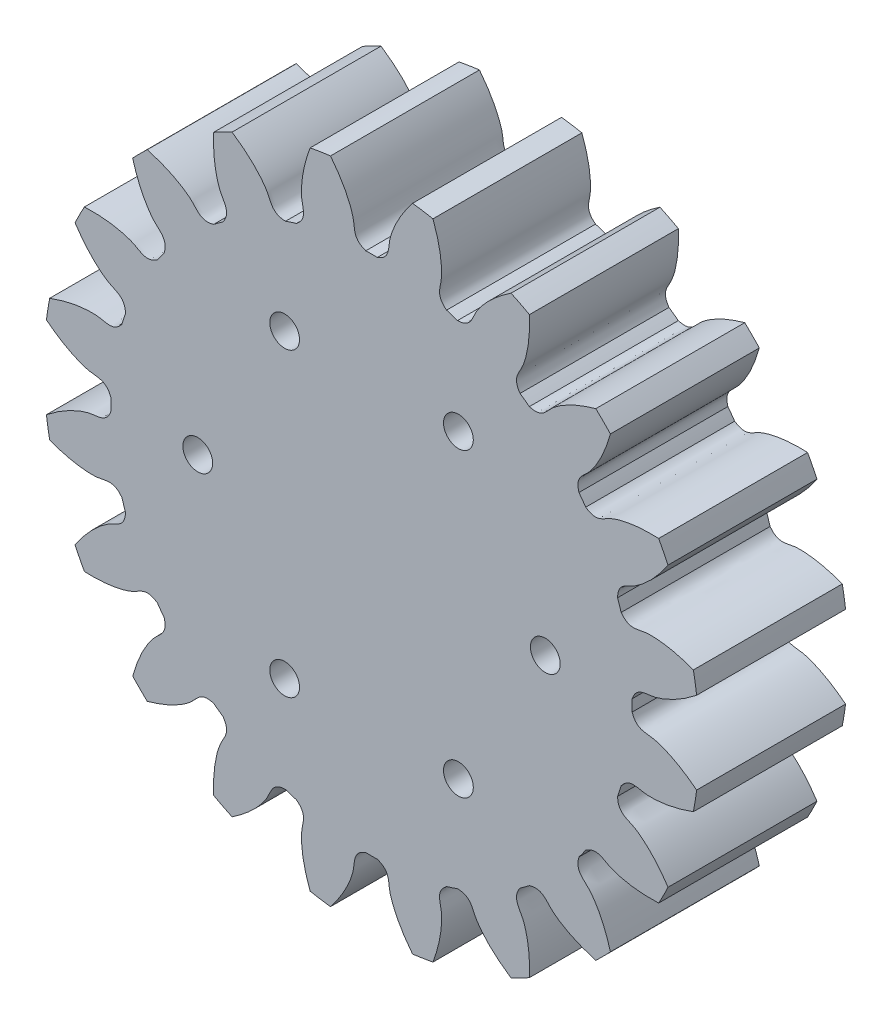
SolidWorks part; units mm, degrees
ref_plane "前视基准面" through (0, 0, 0) normal (0, 0, 1) x (1, 0, 0)
ref_plane "上视基准面" through (0, 0, 0) normal (0, 1, 0) x (1, 0, 0)
ref_plane "右视基准面" through (0, 0, 0) normal (1, 0, 0) x (0, 0, -1)
sketch "草图1" plane through (0, 0, 0) normal (0, 0, 1) x (1, 0, 0)
  circle A0 centre (0, 0) radius 66
extrude "凸台-拉伸1" add sketch "草图1" along normal blind 30
ref_axis "基准轴1" through (0, 0, -1.5) along (0, 0, 1)
sketch "草图2" plane through (0, 0, 0) normal (0, 0, 1) x (1, 0, 0)
  line L0 (0, 0) -> (0, 66) construction
  circle A0 centre (0, 0) radius 66 construction
  arc A1 (1.1599, 52.4872) -> (-1.1599, 52.4872) centre (0, 0) ccw
  arc A2 (19.0869, 74.9895) -> (-19.0869, 74.9895) centre (0, 0) ccw
  spline S0 degree 3 poles (1.1599, 52.4872) (3.6671, 53.3609) (3.3425, 55.1227) (3.6774, 56.8201) (3.7134, 56.9853) (3.7579, 57.1718) (3.8118, 57.3792) (3.8759, 57.6071) (3.9511, 57.8554) (4.0382, 58.1235) (4.138, 58.4111) (4.2514, 58.7179) (4.3791, 59.0433) (4.522, 59.3869) (4.6808, 59.7483) (4.8562, 60.1268) (5.0491, 60.5221) (5.2601, 60.9335) (5.49, 61.3604) (5.7395, 61.8023) (6.0092, 62.2586) (6.2999, 62.7285) (6.6121, 63.2115) (6.9466, 63.7068) (7.3039, 64.2138) (7.6846, 64.7317) (8.0893, 65.2598) (8.5185, 65.7973) (8.9729, 66.3435) (9.4528, 66.8975) (9.9589, 67.4586) (10.4914, 68.0259) (11.051, 68.5985) (11.638, 69.1757) (12.2528, 69.7564) (12.8958, 70.34) (13.5674, 70.9254) (14.2678, 71.5117) (14.9974, 72.098) (15.7564, 72.6834) (16.5451, 73.2669) (17.6488, 74.0498) (18.5036, 74.618) (19.0869, 74.9895) knots 0 0 0 0 0.165916 0.170906 0.176664 0.183189 0.190482 0.198542 0.207371 0.216967 0.22733 0.238462 0.250361 0.263027 0.276462 0.290664 0.305634 0.321371 0.337876 0.355149 0.37319 0.391998 0.411574 0.431917 0.453028 0.474907 0.497554 0.520968 0.54515 0.570099 0.595817 0.622302 0.649554 0.677575 0.706363 0.735918 0.766242 0.797333 0.829191 0.861818 0.895212 0.929373 1 1 1 1
  spline S1 degree 3 poles (-1.1599, 52.4872) (-3.6671, 53.3609) (-3.3425, 55.1227) (-3.6774, 56.8201) (-3.7134, 56.9853) (-3.7579, 57.1718) (-3.8118, 57.3792) (-3.8759, 57.6071) (-3.9511, 57.8554) (-4.0382, 58.1235) (-4.138, 58.4111) (-4.2514, 58.7179) (-4.3791, 59.0433) (-4.522, 59.3869) (-4.6808, 59.7483) (-4.8562, 60.1268) (-5.0491, 60.5221) (-5.2601, 60.9335) (-5.49, 61.3604) (-5.7395, 61.8023) (-6.0092, 62.2586) (-6.2999, 62.7285) (-6.6121, 63.2115) (-6.9466, 63.7068) (-7.3039, 64.2138) (-7.6846, 64.7317) (-8.0893, 65.2598) (-8.5185, 65.7973) (-8.9729, 66.3435) (-9.4528, 66.8975) (-9.9589, 67.4586) (-10.4914, 68.0259) (-11.051, 68.5985) (-11.638, 69.1757) (-12.2528, 69.7564) (-12.8958, 70.34) (-13.5674, 70.9254) (-14.2678, 71.5117) (-14.9974, 72.098) (-15.7564, 72.6834) (-16.5451, 73.2669) (-17.6488, 74.0498) (-18.5036, 74.618) (-19.0869, 74.9895) knots 0 0 0 0 0.165916 0.170906 0.176664 0.183189 0.190482 0.198542 0.207371 0.216967 0.22733 0.238462 0.250361 0.263027 0.276462 0.290664 0.305634 0.321371 0.337876 0.355149 0.37319 0.391998 0.411574 0.431917 0.453028 0.474907 0.497554 0.520968 0.54515 0.570099 0.595817 0.622302 0.649554 0.677575 0.706363 0.735918 0.766242 0.797333 0.829191 0.861818 0.895212 0.929373 1 1 1 1
extrude "切除-拉伸1" cut sketch "草图2" along normal through all
pattern_circular "阵列(圆周)1" count 20 every 18 about axis through (0, 0, -1.5) along (0, 0, 1) of "切除-拉伸1"
sketch "草图3" plane through (0, 0, 0) normal (0, 0, 1) x (1, 0, 0)
  circle A0 centre (0, 0) radius 60 construction
  dimension "Dn" = 120
sketch "草图4" plane through (0, 0, 30) normal (0, 0, 1) x (1, 0, 0)
  circle A0 centre (0, 0) radius 35
  circle A1 centre (-35, 0) radius 3
  circle A2 centre (-17.5, 30.3109) radius 3
  circle A3 centre (17.5, 30.3109) radius 3
  circle A4 centre (35, 0) radius 3
  circle A5 centre (17.5, -30.3109) radius 3
  circle A6 centre (-17.5, -30.3109) radius 3
  point P18 (0, 0)
  dimension "D1" = 70
  dimension "D2" = 6
extrude "切除-拉伸3" cut sketch "草图4" against normal blind 100 contours A1 | A2 | A3 | A4 | A5 | A6
